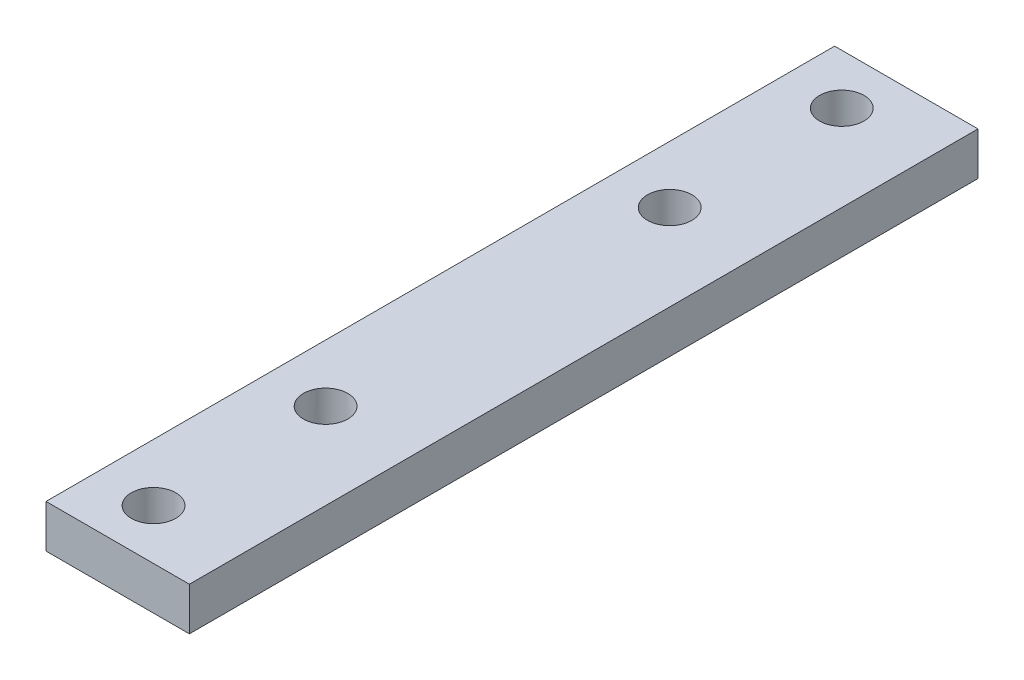
SolidWorks part; units mm, degrees
ref_plane "Front Plane" through (0, 0, 0) normal (0, 0, 1) x (1, 0, 0)
ref_plane "Top Plane" through (0, 0, 0) normal (0, 1, 0) x (1, 0, 0)
ref_plane "Right Plane" through (0, 0, 0) normal (1, 0, 0) x (0, 0, -1)
sketch "Sketch1" plane through (0, 0, 0) normal (0, 0, 1) x (1, 0, 0)
  line L0 (-35, 0) -> (35, 0)
  circle A0 centre (0, 0) radius 35
  dimension "D1" = 70
extrude "Boss-Extrude1" add sketch "Sketch1" along normal blind 45 contours L0 A0 region at (0, -14.8545, 0)
sketch "Sketch2" plane through (0, 0, 0) normal (0, 1, 0) x (1, 0, 0)
  line L0 (-35, 0) -> (35, 0) construction
  line L1 (-31, -4) -> (0.5147, -4)
  line L2 (-31, -4) -> (-31, -41)
  line L3 (-31, -41) -> (0, -41)
  line L5 (-35, -45) -> (35, -45) construction
  line L6 (-35, -45) -> (-35, 0) construction
  line L7 (0, 0) -> (0, -45) construction
  line L8 (-31, -4) -> (0.5147, -4)
  line L9 (-31, -4) -> (-31, -41)
  line L10 (-31, -41) -> (0, -41)
  line L13 (-31, -4) -> (0, -4)
  line L14 (-31, -4) -> (-31, -41)
  line L15 (-31, -41) -> (0, -41)
  line L16 (0, -4) -> (0, -41)
  dimension "D1" = 4
  dimension "D2" = 4
  dimension "D3" = 4
ref_axis "Axis1" through (0, 0, 45) along (0, 0, -1)
revolve "Cut-Revolve1" cut sketch "Sketch2" angle 360 about L7 region at (-15.5, 0, 22.5)
sketch "Sketch3" plane through (0, 0, 45) normal (0, 0, 1) x (1, 0, 0)
  line L0 (-17.5, 0) -> (-17.5, -35)
  line L1 (0, 0) -> (-35, 0)
  line L4 (0, 0) -> (0, -35)
  line L9 (-35, -35) -> (-17.5, -35)
  line L10 (-35, 0) -> (-35, -35)
  line L11 (-35, 0) -> (-17.5, 0)
  line L12 (-35, -35) -> (0, -35)
  line L13 (-35, 0) -> (-35, -35)
  arc A0 (-35, 0) -> (35, 0) centre (0, 0) ccw construction
  line M1 (35, 0) -> (-35, 0)
  arc M2 (-35, 0) -> (35, 0) centre (0, 0) ccw
extrude "Boss-Extrude3" add sketch "Sketch3" against normal blind 45 contours L10 L9 L0 M2 | L0 L12 M2 | L0 M1 M2 region at (-24.6757, -11.8721, 45) region at (-13.1858, -33.611, 45) region at (-28.7561, -26.4591, 45)
sketch "Sketch4" plane through (-35, 0, 0) normal (-1, 0, 0) x (0, 0, 1)
  line L0 (0, -35) -> (45, -35) construction
  line L2 (0, 0) -> (0, -35) construction
  line L3 (0, 0) -> (45, 0) construction
  line L4 (45, 0) -> (22.5, 0) construction
  line L5 (22.5, 0) -> (22.5, -35) construction
  circle A0 centre (10, -17.5) radius 5.05
  circle A1 centre (35, -17.5) radius 5.05
  dimension "D1" = 10.1
  dimension "D2" = 17.5
  dimension "D3" = 10
extrude "Cut-Extrude1" cut sketch "Sketch4" against normal blind 12
sketch "Sketch5" plane through (0, 0, 0) normal (0, 0, -1) x (-1, 0, 0)
  line L0 (35, -35) -> (0, -35) construction
  line L1 (35, 0) -> (30, 0)
  line L2 (35, 0) -> (35, -35)
  line L3 (35, -35) -> (30, -35)
  line L4 (30, 0) -> (30, -35)
  dimension "D1" = 5
extrude "Cut-Extrude2" cut sketch "Sketch5" against normal through all
sketch "Sketch6" plane through (0, 0, 41) normal (0, 0, -1) x (-1, 0, 0)
  line L0 (0, -31) -> (0, 0)
  line L1 (0, 0) -> (-31, 0)
  line L2 (0, 0) -> (-12.5, 0)
  line L3 (-12.5, 0) -> (-12.5, -28.3681)
  line L5 (17.5, 0) -> (12.5, 0)
  line L6 (17.5, 0) -> (17.5, -28.3681)
  line L7 (17.5, -28.3681) -> (12.5, -28.3681)
  line L8 (12.5, 0) -> (12.5, -28.3681)
  circle A0 centre (0, 0) radius 31
  line M1 (17.5, -25.5881) -> (17.5, 0)
  line M2 (17.5, 0) -> (-31, 0)
  arc M3 (-31, 0) -> (17.5, -25.5881) centre (0, 0) ccw
  dimension "D1" = 12.5
  dimension "D2" = 5
extrude "Boss-Extrude5" add sketch "Sketch6" along normal blind 37 contours L3 L1 M3 | L8 M2 M3 M1 region at (20.1294, -11.2411, 41) region at (-14.9573, -13.5514, 41)
sketch "Sketch7" plane through (0, 0, 0) normal (0, 0, -1) x (-1, 0, 0)
  line L5 (-35, 0) -> (-12.5, 0)
  line L6 (-35, 0) -> (-35, -7.441)
  line L7 (-35, -7.441) -> (-12.5, -7.441)
  line L8 (-12.5, 0) -> (-12.5, -7.441)
  line L9 (0, 0) -> (0, 11.2128) construction
  line L10 (35, 0) -> (35, -7.441)
  line L11 (35, 0) -> (12.5, 0)
  line L12 (35, -7.441) -> (12.5, -7.441)
  line L13 (12.5, 0) -> (12.5, -7.441)
  circle A0 centre (0, 0) radius 35
  line M6 (30, -35) -> (30, 0)
  line M7 (30, 0) -> (-35, 0)
  arc M8 (-35, 0) -> (0, -35) centre (0, 0) ccw
  dimension "D1" = 22.5
extrude "Boss-Extrude6" add sketch "Sketch7" along normal blind 5 contours L8 L7 M7 M8 | L13 L12 M7 M6 region at (23.6185, -3.6982, 0) region at (-21.25, -3.7205, 0)
ref_plane "Plane1" through (0, 0, 22.5) normal (0, 0, -1) x (-1, 0, 0)
mirror "Mirror1" about plane through (0, 0, 22.5) normal (0, 0, -1) of "Boss-Extrude6"
sketch "Sketch9" plane through (0, 0, 0) normal (0, 1, 0) x (1, 0, 0)
  line L0 (12.5, -50) -> (35, -50) construction
  line L5 (35, 5) -> (20, 5)
  line L6 (35, 5) -> (35, -50)
  line L7 (35, -50) -> (20, -50)
  line L8 (20, 5) -> (20, -50)
  line L9 (-30, -50) -> (-12.5, -50) construction
  line L10 (-30, 5) -> (-20, 5)
  line L11 (-30, 5) -> (-30, -50)
  line L12 (-30, -50) -> (-20, -50)
  line L13 (-20, 5) -> (-20, -50)
  dimension "D1" = 10
  dimension "D2" = 15
extrude "Boss-Extrude7" add sketch "Sketch9" along normal blind 3
sketch "Sketch12" plane through (0, 3, 0) normal (0, 1, 0) x (1, 0, 0)
  line L0 (35, -50) -> (35, 5) construction
  line L1 (35, 5) -> (20, 5) construction
  line L3 (19.25, -22.5) -> (-19.25, -22.5) construction
  line L4 (35, -22.5) -> (0, -22.5) construction
  line L6 (-30, 5) -> (-30, -50) construction
  line L7 (0, -22.5) -> (0, -55.2431) construction
  circle A0 centre (26, 1.5) radius 1.55
  circle A1 centre (26, -10.5) radius 1.55
  circle A2 centre (26, -34.5) radius 1.55
  circle A3 centre (26, -46.5) radius 1.55
  circle A7 centre (-26, 1.5) radius 1.55
  circle A8 centre (-26, -10.5) radius 1.55
  circle A9 centre (-26, -34.5) radius 1.55
  circle A10 centre (-26, -46.5) radius 1.55
  dimension "D1" = 3.1
  dimension "D2" = 9
  dimension "D3" = 3.5
  dimension "D4" = 12
  dimension "D5" = 9
  dimension "D6" = 3.1
  dimension "D7" = 4
  dimension "D8" = 2
extrude "Cut-Extrude5" cut sketch "Sketch12" against normal blind 5
sketch "Sketch13" plane through (35, 0, 0) normal (1, 0, 0) x (0, 0, -1)
  line L1 (-50, 3) -> (-43, 3)
  line L2 (-50, 3) -> (-50, -4)
  line L3 (-50, -4) -> (-43, -4)
  line L4 (-43, 3) -> (-43, -4)
  line L6 (-44.95, -2) -> (-44.95, 3) construction
  line L7 (-44.95, -2) -> (-48.05, -2) construction
  line L8 (-50, 3) -> (5, 3) construction
  line L9 (-38, 3) -> (-31, 3)
  line L10 (-38, 3) -> (-38, -4)
  line L11 (-38, -4) -> (-31, -4)
  line L12 (-31, 3) -> (-31, -4)
  line L13 (-36.05, 3) -> (-36.05, -2) construction
  line L14 (-32.95, -2) -> (-32.95, 3) construction
  line L15 (-32.95, -2) -> (-36.05, -2) construction
  line L16 (-22.5, 3) -> (-22.5, 8.3556) construction
  line L17 (-22.5, -19.25) -> (-22.5, 19.25) construction
  line L18 (-14, 3) -> (-14, -4)
  line L19 (-7, -4) -> (-14, -4)
  line L20 (-7, 3) -> (-7, -4)
  line L21 (-7, 3) -> (-14, 3)
  line L22 (-2, 3) -> (-2, -4)
  line L23 (5, -4) -> (-2, -4)
  line L24 (5, 3) -> (5, -4)
  line L25 (5, 3) -> (-2, 3)
  line L27 (-50, 3) -> (5, 3)
  line L28 (-50, 3) -> (-50, 0)
  line L29 (-50, 0) -> (5, 0)
  line L30 (5, 3) -> (5, 0)
  line M9 (-50, 0) -> (5, 0)
  dimension "D1" = 1.95
  dimension "D2" = 2
  dimension "D3" = 1.95
  dimension "D4" = 1.95
  dimension "D5" = 2
extrude "Cut-Extrude6" cut sketch "Sketch13" against normal through all contours L4 L2 L3 M9 | L12 L10 L11 M9 | L20 L18 L19 M9 | L24 L22 L23 M9 region at (35, -2, 46.5) region at (35, -2, 34.5) region at (35, -2, 10.5) region at (35, -2, -1.5)
sketch "Sketch14" plane through (0, 0, 50) normal (0, 0, 1) x (1, 0, 0)
  line L1 (-30, 0) -> (17.5204, 0)
  line L2 (-30, 0) -> (-30, -35.4874)
  line L3 (-30, -35.4874) -> (35.3006, -35.4874)
  line L4 (35.3006, 0) -> (35.3006, -35.4874)
  line L6 (35.3006, 0) -> (35.3006, 7.5728)
  line L7 (35.3006, 7.5728) -> (17.5204, 7.5728)
  line L8 (17.5204, 0) -> (17.5204, 7.5728)
extrude "Cut-Extrude7" cut sketch "Sketch14" against normal through all
